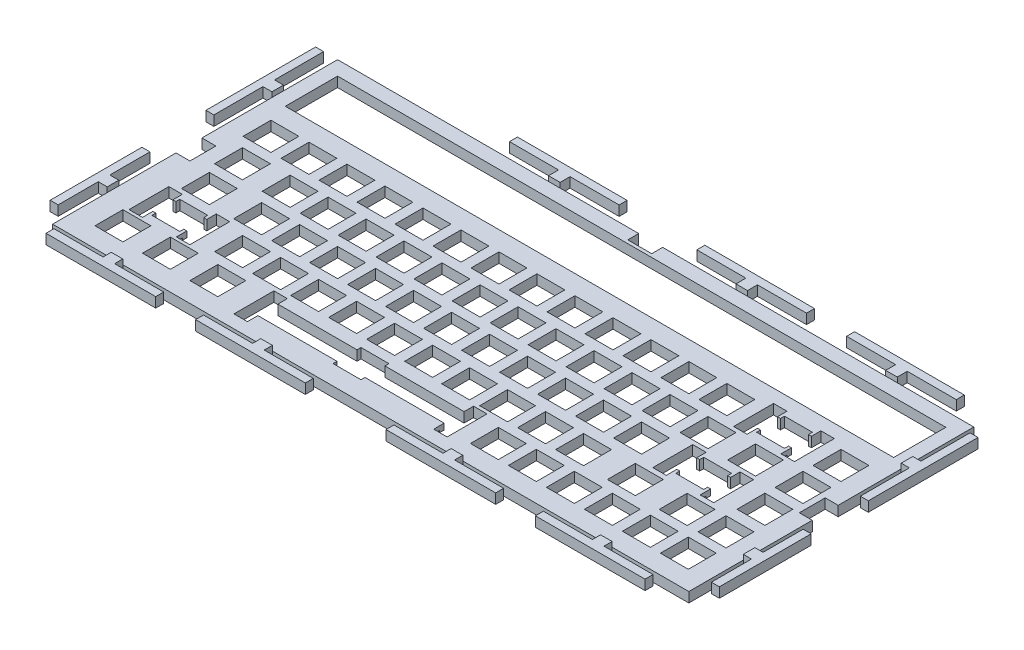
SolidWorks part; units mm, degrees
ref_plane "Front Plane" through (0, 0, 0) normal (0, 0, 1) x (1, 0, 0)
ref_plane "Top Plane" through (0, 0, 0) normal (0, 1, 0) x (1, 0, 0)
ref_plane "Right Plane" through (0, 0, 0) normal (1, 0, 0) x (0, 0, -1)
sketch "Sketch1" plane through (0, 0, 0) normal (0, 1, 0) x (1, 0, 0)
  line L2 (-75.7545, 37.9956) -> (-61.7545, 37.9956)
  line L3 (-94.8265, 37.9956) -> (-80.8265, 37.9956)
  line L4 (-94.8265, 37.9956) -> (-94.8265, 51.9956)
  line L5 (-94.8265, 51.9956) -> (-80.8265, 51.9956)
  line L6 (-80.8265, 37.9956) -> (-80.8265, 51.9956)
  line L7 (-75.7545, 37.9956) -> (-75.7545, 51.9956)
  line L8 (-75.7545, 51.9956) -> (-61.7545, 51.9956)
  line L9 (-61.7545, 37.9956) -> (-61.7545, 51.9956)
  line L10 (133.7495, 37.9956) -> (147.7495, 37.9956)
  line L11 (-37.6545, 37.9956) -> (-23.6545, 37.9956)
  line L12 (-56.7045, 37.9956) -> (-42.7045, 37.9956)
  line L13 (-56.7045, 37.9956) -> (-56.7045, 51.9956)
  line L14 (-56.7045, 51.9956) -> (-42.7045, 51.9956)
  line L15 (-42.7045, 37.9956) -> (-42.7045, 51.9956)
  line L16 (-37.6545, 37.9956) -> (-37.6545, 51.9956)
  line L17 (-37.6545, 51.9956) -> (-23.6545, 51.9956)
  line L18 (-23.6545, 37.9956) -> (-23.6545, 51.9956)
  line L19 (133.7495, 37.9956) -> (133.7495, 51.9956)
  line L20 (133.7495, 51.9956) -> (147.7495, 51.9956)
  line L21 (0.4455, 37.9956) -> (14.4455, 37.9956)
  line L22 (-18.6045, 37.9956) -> (-4.6045, 37.9956)
  line L23 (-18.6045, 37.9956) -> (-18.6045, 51.9956)
  line L24 (-18.6045, 51.9956) -> (-4.6045, 51.9956)
  line L25 (-4.6045, 37.9956) -> (-4.6045, 51.9956)
  line L26 (0.4455, 37.9956) -> (0.4455, 51.9956)
  line L27 (0.4455, 51.9956) -> (14.4455, 51.9956)
  line L28 (14.4455, 37.9956) -> (14.4455, 51.9956)
  line L29 (147.7495, 37.9956) -> (147.7495, 51.9956)
  line L30 (38.5455, 37.9956) -> (52.5455, 37.9956)
  line L31 (19.4955, 37.9956) -> (33.4955, 37.9956)
  line L32 (19.4955, 37.9956) -> (19.4955, 51.9956)
  line L33 (19.4955, 51.9956) -> (33.4955, 51.9956)
  line L34 (33.4955, 37.9956) -> (33.4955, 51.9956)
  line L35 (38.5455, 37.9956) -> (38.5455, 51.9956)
  line L36 (38.5455, 51.9956) -> (52.5455, 51.9956)
  line L37 (52.5455, 37.9956) -> (52.5455, 51.9956)
  line L38 (147.7495, 44.9956) -> (154.1495, 44.9956) construction
  line L39 (167.1835, 18.9456) -> (181.1835, 18.9456)
  line L40 (167.1835, 18.9456) -> (167.1835, 32.9456)
  line L41 (76.6455, 37.9956) -> (90.6455, 37.9956)
  line L42 (57.5955, 37.9956) -> (71.5955, 37.9956)
  line L43 (57.5955, 37.9956) -> (57.5955, 51.9956)
  line L44 (57.5955, 51.9956) -> (71.5955, 51.9956)
  line L45 (71.5955, 37.9956) -> (71.5955, 51.9956)
  line L46 (76.6455, 37.9956) -> (76.6455, 51.9956)
  line L47 (76.6455, 51.9956) -> (90.6455, 51.9956)
  line L48 (90.6455, 37.9956) -> (90.6455, 51.9956)
  line L49 (167.1835, 32.9456) -> (181.1835, 32.9456)
  line L50 (114.7225, 37.9956) -> (128.7225, 37.9956)
  line L51 (95.6955, 37.9956) -> (109.6955, 37.9956)
  line L52 (95.6955, 37.9956) -> (95.6955, 51.9956)
  line L53 (95.6955, 51.9956) -> (109.6955, 51.9956)
  line L54 (109.6955, 37.9956) -> (109.6955, 51.9956)
  line L55 (114.7225, 37.9956) -> (114.7225, 51.9956)
  line L56 (114.7225, 51.9956) -> (128.7225, 51.9956)
  line L57 (128.7225, 37.9956) -> (128.7225, 51.9956)
  line L58 (181.1835, 18.9456) -> (181.1835, 32.9456)
  line L59 (157.3735, 25.9456) -> (167.1835, 25.9456) construction
  line L73 (162.3995, 52.2456) -> (176.3995, 52.2456)
  line L75 (176.3995, 38.2456) -> (162.3995, 38.2456)
  line L77 (176.3995, 52.2456) -> (176.3995, 50.2456)
  line L78 (176.3995, 50.2456) -> (177.8995, 50.2456)
  line L79 (177.8995, 50.2456) -> (177.8995, 54.9956)
  line L80 (177.8995, 54.9956) -> (184.6495, 54.9956)
  line L81 (184.6495, 54.9956) -> (184.6495, 34.9956)
  line L82 (184.6495, 34.9956) -> (177.8995, 34.9956)
  line L83 (177.8995, 34.9956) -> (177.8995, 40.2456)
  line L84 (177.8995, 40.2456) -> (176.3995, 40.2456)
  line L85 (176.3995, 40.2456) -> (176.3995, 38.2456)
  line L86 (162.3995, 52.2456) -> (162.3995, 50.2456)
  line L87 (160.8995, 54.9956) -> (160.8995, 50.2456)
  line L88 (160.8995, 50.2456) -> (162.3995, 50.2456)
  line L89 (160.8995, 54.9956) -> (154.1495, 54.9956)
  line L90 (154.1495, 54.9956) -> (154.1495, 34.9956)
  line L91 (154.1495, 34.9956) -> (160.8995, 34.9956)
  line L92 (160.8995, 34.9956) -> (160.8995, 40.2456)
  line L93 (160.8995, 40.2456) -> (162.3995, 40.2456)
  line L94 (162.3995, 40.2456) -> (162.3995, 38.2456)
  line L116 (-47.1265, 18.9456) -> (-33.1265, 18.9456)
  line L117 (-66.1765, 18.9456) -> (-52.1765, 18.9456)
  line L118 (-66.1765, 18.9456) -> (-66.1765, 32.9456)
  line L119 (-66.1765, 32.9456) -> (-52.1765, 32.9456)
  line L120 (-52.1765, 18.9456) -> (-52.1765, 32.9456)
  line L121 (-47.1265, 18.9456) -> (-47.1265, 32.9456)
  line L122 (-47.1265, 32.9456) -> (-33.1265, 32.9456)
  line L123 (-33.1265, 18.9456) -> (-33.1265, 32.9456)
  line L125 (-9.0515, 18.9456) -> (4.9485, 18.9456)
  line L126 (-28.0765, 18.9456) -> (-14.0765, 18.9456)
  line L127 (-28.0765, 18.9456) -> (-28.0765, 32.9456)
  line L128 (-28.0765, 32.9456) -> (-14.0765, 32.9456)
  line L129 (-14.0765, 18.9456) -> (-14.0765, 32.9456)
  line L130 (-9.0515, 18.9456) -> (-9.0515, 32.9456)
  line L131 (-9.0515, 32.9456) -> (4.9485, 32.9456)
  line L132 (4.9485, 18.9456) -> (4.9485, 32.9456)
  line L135 (29.0735, 18.9456) -> (43.0735, 18.9456)
  line L136 (9.9485, 18.9456) -> (23.9485, 18.9456)
  line L137 (9.9485, 18.9456) -> (9.9485, 32.9456)
  line L138 (9.9485, 32.9456) -> (23.9485, 32.9456)
  line L139 (23.9485, 18.9456) -> (23.9485, 32.9456)
  line L140 (29.0735, 18.9456) -> (29.0735, 32.9456)
  line L141 (29.0735, 32.9456) -> (43.0735, 32.9456)
  line L142 (43.0735, 18.9456) -> (43.0735, 32.9456)
  line L144 (67.1485, 18.9456) -> (81.1485, 18.9456)
  line L145 (48.1235, 18.9456) -> (62.1235, 18.9456)
  line L146 (48.1235, 18.9456) -> (48.1235, 32.9456)
  line L147 (48.1235, 32.9456) -> (62.1235, 32.9456)
  line L148 (62.1235, 18.9456) -> (62.1235, 32.9456)
  line L149 (67.1485, 18.9456) -> (67.1485, 32.9456)
  line L150 (67.1485, 32.9456) -> (81.1485, 32.9456)
  line L151 (81.1485, 18.9456) -> (81.1485, 32.9456)
  line L152 (159.9865, 14.1456) -> (173.9865, 14.1456)
  line L153 (-42.3635, -0.1044) -> (-28.3635, -0.1044)
  line L154 (-61.4135, -0.1044) -> (-47.4135, -0.1044)
  line L155 (105.2735, 18.9456) -> (119.2735, 18.9456)
  line L156 (86.2235, 18.9456) -> (100.2235, 18.9456)
  line L157 (86.2235, 18.9456) -> (86.2235, 32.9456)
  line L158 (86.2235, 32.9456) -> (100.2235, 32.9456)
  line L159 (100.2235, 18.9456) -> (100.2235, 32.9456)
  line L160 (105.2735, 18.9456) -> (105.2735, 32.9456)
  line L161 (105.2735, 32.9456) -> (119.2735, 32.9456)
  line L162 (119.2735, 18.9456) -> (119.2735, 32.9456)
  line L163 (-61.4135, -0.1044) -> (-61.4135, 13.8956)
  line L172 (-94.8265, 37.9956) -> (-94.8265, 32.9456) construction
  line L173 (-61.4135, 13.8956) -> (-47.4135, 13.8956)
  line L174 (-47.4135, -0.1044) -> (-47.4135, 13.8956)
  line L175 (-90.0635, 18.9456) -> (-76.0635, 18.9456)
  line L176 (-90.0635, 18.9456) -> (-90.0635, 32.9456)
  line L177 (-90.0635, 32.9456) -> (-76.0635, 32.9456)
  line L178 (-76.0635, 18.9456) -> (-76.0635, 32.9456)
  line L179 (-94.8265, 32.9456) -> (-90.0635, 32.9456) construction
  line L180 (124.3235, 18.9456) -> (138.3235, 18.9456)
  line L185 (124.3235, 18.9456) -> (124.3235, 32.9456)
  line L186 (124.3235, 32.9456) -> (138.3235, 32.9456)
  line L187 (138.3235, 18.9456) -> (138.3235, 32.9456)
  line L188 (-42.3635, -0.1044) -> (-42.3635, 13.8956)
  line L189 (143.3735, 18.9456) -> (157.3735, 18.9456)
  line L190 (143.3735, 18.9456) -> (143.3735, 32.9456)
  line L191 (143.3735, 32.9456) -> (157.3735, 32.9456)
  line L192 (157.3735, 18.9456) -> (157.3735, 32.9456)
  line L193 (-42.3635, 13.8956) -> (-28.3635, 13.8956)
  line L194 (-28.3635, -0.1044) -> (-28.3635, 13.8956)
  line L195 (-4.2635, -0.1044) -> (9.7365, -0.1044)
  line L196 (-23.3135, -0.1044) -> (-9.3135, -0.1044)
  line L197 (-23.3135, -0.1044) -> (-23.3135, 13.8956)
  line L198 (-23.3135, 13.8956) -> (-9.3135, 13.8956)
  line L199 (-9.3135, -0.1044) -> (-9.3135, 13.8956)
  line L200 (-4.2635, -0.1044) -> (-4.2635, 13.8956)
  line L201 (-4.2635, 13.8956) -> (9.7365, 13.8956)
  line L202 (9.7365, -0.1044) -> (9.7365, 13.8956)
  line L203 (33.8365, -0.1044) -> (47.8365, -0.1044)
  line L204 (14.7865, -0.1044) -> (28.7865, -0.1044)
  line L205 (14.7865, -0.1044) -> (14.7865, 13.8956)
  line L206 (14.7865, 13.8956) -> (28.7865, 13.8956)
  line L207 (28.7865, -0.1044) -> (28.7865, 13.8956)
  line L208 (33.8365, -0.1044) -> (33.8365, 13.8956)
  line L209 (33.8365, 13.8956) -> (47.8365, 13.8956)
  line L210 (47.8365, -0.1044) -> (47.8365, 13.8956)
  line L211 (71.9365, -0.1044) -> (85.9365, -0.1044)
  line L212 (52.8865, -0.1044) -> (66.8865, -0.1044)
  line L213 (52.8865, -0.1044) -> (52.8865, 13.8956)
  line L214 (52.8865, 13.8956) -> (66.8865, 13.8956)
  line L215 (66.8865, -0.1044) -> (66.8865, 13.8956)
  line L216 (71.9365, -0.1044) -> (71.9365, 13.8956)
  line L217 (71.9365, 13.8956) -> (85.9365, 13.8956)
  line L218 (85.9365, -0.1044) -> (85.9365, 13.8956)
  line L219 (110.0365, -0.1044) -> (124.0365, -0.1044)
  line L220 (90.9865, -0.1044) -> (104.9865, -0.1044)
  line L221 (90.9865, -0.1044) -> (90.9865, 13.8956)
  line L222 (90.9865, 13.8956) -> (104.9865, 13.8956)
  line L223 (104.9865, -0.1044) -> (104.9865, 13.8956)
  line L224 (110.0365, -0.1044) -> (110.0365, 13.8956)
  line L225 (110.0365, 13.8956) -> (124.0365, 13.8956)
  line L226 (124.0365, -0.1044) -> (124.0365, 13.8956)
  line L227 (-87.6075, -0.1044) -> (-73.6075, -0.1044)
  line L228 (-87.6075, -0.1044) -> (-87.6075, 13.8956)
  line L229 (-87.6075, 13.8956) -> (-73.6075, 13.8956)
  line L230 (-73.6075, -0.1044) -> (-73.6075, 13.8956)
  line L231 (-90.0635, 18.9456) -> (-90.0635, 13.8956) construction
  line L232 (129.0865, -0.1044) -> (143.0865, -0.1044)
  line L233 (129.0865, -0.1044) -> (129.0865, 13.8956)
  line L234 (129.0865, 13.8956) -> (143.0865, 13.8956)
  line L235 (143.0865, -0.1044) -> (143.0865, 13.8956)
  line L240 (-90.0635, 13.8956) -> (-87.6075, 13.8956) construction
  line L241 (173.9865, 0.1456) -> (159.9865, 0.1456)
  line L242 (173.9865, 14.1456) -> (173.9865, 12.1456)
  line L243 (173.9865, 12.1456) -> (175.4865, 12.1456)
  line L244 (175.4865, 12.1456) -> (175.4865, 16.8956)
  line L245 (175.4865, 16.8956) -> (182.2365, 16.8956)
  line L246 (182.2365, 16.8956) -> (182.2365, -3.1044)
  line L247 (182.2365, -3.1044) -> (175.4865, -3.1044)
  line L248 (175.4865, -3.1044) -> (175.4865, 2.1456)
  line L249 (175.4865, 2.1456) -> (173.9865, 2.1456)
  line L250 (173.9865, 2.1456) -> (173.9865, 0.1456)
  line L251 (159.9865, 14.1456) -> (159.9865, 12.1456)
  line L252 (158.4865, 16.8956) -> (158.4865, 12.1456)
  line L253 (158.4865, 12.1456) -> (159.9865, 12.1456)
  line L254 (158.4865, 16.8956) -> (151.7365, 16.8956)
  line L255 (151.7365, 16.8956) -> (151.7365, -3.1044)
  line L256 (151.7365, -3.1044) -> (158.4865, -3.1044)
  line L257 (158.4865, -3.1044) -> (158.4865, 2.1456)
  line L258 (158.4865, 2.1456) -> (159.9865, 2.1456)
  line L259 (159.9865, 2.1456) -> (159.9865, 0.1456)
  line L260 (143.0865, 12.1456) -> (151.7365, 12.1456) construction
  line L262 (-32.8385, -19.1544) -> (-18.8385, -19.1544)
  line L263 (-51.8885, -19.1544) -> (-37.8885, -19.1544)
  line L264 (-51.8885, -19.1544) -> (-51.8885, -5.1544)
  line L265 (-51.8885, -5.1544) -> (-37.8885, -5.1544)
  line L266 (-37.8885, -19.1544) -> (-37.8885, -5.1544)
  line L267 (-32.8385, -19.1544) -> (-32.8385, -5.1544)
  line L268 (-32.8385, -5.1544) -> (-18.8385, -5.1544)
  line L269 (-18.8385, -19.1544) -> (-18.8385, -5.1544)
  line L270 (5.2615, -19.1544) -> (19.2615, -19.1544)
  line L271 (-13.7885, -19.1544) -> (0.2115, -19.1544)
  line L272 (-13.7885, -19.1544) -> (-13.7885, -5.1544)
  line L273 (-13.7885, -5.1544) -> (0.2115, -5.1544)
  line L274 (0.2115, -19.1544) -> (0.2115, -5.1544)
  line L275 (5.2615, -19.1544) -> (5.2615, -5.1544)
  line L276 (5.2615, -5.1544) -> (19.2615, -5.1544)
  line L277 (19.2615, -19.1544) -> (19.2615, -5.1544)
  line L278 (43.3615, -19.1544) -> (57.3615, -19.1544)
  line L279 (24.3115, -19.1544) -> (38.3115, -19.1544)
  line L280 (24.3115, -19.1544) -> (24.3115, -5.1544)
  line L281 (24.3115, -5.1544) -> (38.3115, -5.1544)
  line L282 (38.3115, -19.1544) -> (38.3115, -5.1544)
  line L283 (43.3615, -19.1544) -> (43.3615, -5.1544)
  line L284 (43.3615, -5.1544) -> (57.3615, -5.1544)
  line L285 (57.3615, -19.1544) -> (57.3615, -5.1544)
  line L286 (81.4615, -19.6544) -> (95.4615, -19.6544)
  line L287 (62.4115, -19.6544) -> (76.4115, -19.6544)
  line L288 (62.4115, -19.6544) -> (62.4115, -5.6544)
  line L289 (62.4115, -5.6544) -> (76.4115, -5.6544)
  line L290 (76.4115, -19.6544) -> (76.4115, -5.6544)
  line L291 (81.4615, -19.6544) -> (81.4615, -5.6544)
  line L292 (81.4615, -5.6544) -> (95.4615, -5.6544)
  line L293 (95.4615, -19.6544) -> (95.4615, -5.6544)
  line L294 (119.5615, -19.6544) -> (133.5615, -19.6544)
  line L295 (100.5115, -19.6544) -> (114.5115, -19.6544)
  line L296 (100.5115, -19.6544) -> (100.5115, -5.6544)
  line L297 (100.5115, -5.6544) -> (114.5115, -5.6544)
  line L298 (114.5115, -19.6544) -> (114.5115, -5.6544)
  line L299 (119.5615, -19.6544) -> (119.5615, -5.6544)
  line L300 (119.5615, -5.6544) -> (133.5615, -5.6544)
  line L301 (133.5615, -19.6544) -> (133.5615, -5.6544)
  line L306 (-83.3445, -5.1544) -> (-69.3445, -5.1544)
  line L307 (145.5235, -19.6544) -> (159.5235, -19.6544)
  line L308 (145.5235, -19.6544) -> (145.5235, -5.6544)
  line L309 (145.5235, -5.6544) -> (159.5235, -5.6544)
  line L310 (159.5235, -19.6544) -> (159.5235, -5.6544)
  line L311 (-69.3445, -19.1544) -> (-83.3445, -19.1544)
  line L331 (171.4855, -19.6544) -> (185.4855, -19.6544)
  line L332 (171.4855, -19.6544) -> (171.4855, -5.6544)
  line L333 (171.4855, -5.6544) -> (185.4855, -5.6544)
  line L334 (185.4855, -19.6544) -> (185.4855, -5.6544)
  line L335 (159.5235, -12.6544) -> (171.4855, -12.6544) construction
  line L336 (-61.4135, -0.1044) -> (-61.4135, -5.1544) construction
  line L337 (-61.4135, -5.1544) -> (-51.8885, -5.1544) construction
  line L338 (-104.4215, 94.9896) -> (-117.5239, 94.9896) construction
  line L339 (-97.2765, 61.6456) -> (207.7235, 61.6456)
  line L340 (190.9955, 18.9456) -> (204.9955, 18.9456)
  line L341 (190.9955, 18.9456) -> (190.9955, 32.9456)
  line L342 (190.9955, 32.9456) -> (204.9955, 32.9456)
  line L343 (204.9955, 18.9456) -> (204.9955, 32.9456)
  line L344 (181.1835, 25.9456) -> (190.9955, 25.9456) construction
  line L345 (190.9745, 37.9956) -> (204.9745, 37.9956)
  line L346 (190.9745, 37.9956) -> (190.9745, 51.9956)
  line L347 (190.9745, 51.9956) -> (204.9745, 51.9956)
  line L348 (204.9745, 37.9956) -> (204.9745, 51.9956)
  line L349 (184.6495, 44.9956) -> (190.9745, 44.9956) construction
  line L350 (190.9425, -0.1044) -> (204.9425, -0.1044)
  line L351 (190.9425, -0.1044) -> (190.9425, 13.8956)
  line L352 (190.9425, 13.8956) -> (204.9425, 13.8956)
  line L353 (204.9425, -0.1044) -> (204.9425, 13.8956)
  line L354 (182.2365, 6.8956) -> (190.9425, 6.8956) construction
  line L355 (190.9855, -19.6544) -> (204.9855, -19.6544)
  line L356 (190.9855, -19.6544) -> (190.9855, -5.6544)
  line L357 (190.9855, -5.6544) -> (204.9855, -5.6544)
  line L358 (204.9855, -19.6544) -> (204.9855, -5.6544)
  line L359 (185.4855, -12.6544) -> (190.9855, -12.6544) construction
  line L360 (-69.3445, -5.1544) -> (-69.3445, -7.1544)
  line L361 (-69.3445, -7.1544) -> (-67.8445, -7.1544)
  line L362 (-67.8445, -7.1544) -> (-67.8445, -2.4044)
  line L363 (-67.8445, -2.4044) -> (-61.0945, -2.4044)
  line L364 (-61.0945, -2.4044) -> (-61.0945, -22.4044)
  line L365 (-61.0945, -22.4044) -> (-67.8445, -22.4044)
  line L366 (-67.8445, -22.4044) -> (-67.8445, -17.1544)
  line L367 (-67.8445, -17.1544) -> (-69.3445, -17.1544)
  line L368 (-69.3445, -17.1544) -> (-69.3445, -19.1544)
  line L369 (-83.3445, -5.1544) -> (-83.3445, -7.1544)
  line L370 (-84.8445, -2.4044) -> (-84.8445, -7.1544)
  line L371 (-84.8445, -7.1544) -> (-83.3445, -7.1544)
  line L372 (-84.8445, -2.4044) -> (-91.5945, -2.4044)
  line L373 (-91.5945, -2.4044) -> (-91.5945, -22.4044)
  line L374 (-91.5945, -22.4044) -> (-84.8445, -22.4044)
  line L375 (-84.8445, -22.4044) -> (-84.8445, -17.1544)
  line L376 (-84.8445, -17.1544) -> (-83.3445, -17.1544)
  line L377 (-83.3445, -17.1544) -> (-83.3445, -19.1544)
  line L378 (-93.0945, -37.9544) -> (-79.0945, -37.9544)
  line L379 (-93.0945, -37.9544) -> (-93.0945, -23.9544)
  line L380 (-93.0945, -23.9544) -> (-79.0945, -23.9544)
  line L381 (-79.0945, -37.9544) -> (-79.0945, -23.9544)
  line L382 (-69.2945, -37.9544) -> (-55.2945, -37.9544)
  line L383 (-69.2945, -37.9544) -> (-69.2945, -23.9544)
  line L384 (-69.2945, -23.9544) -> (-55.2945, -23.9544)
  line L385 (-55.2945, -37.9544) -> (-55.2945, -23.9544)
  line L390 (-45.4945, -37.9544) -> (-31.4945, -37.9544)
  line L391 (-45.4945, -37.9544) -> (-45.4945, -23.9544)
  line L392 (-45.4945, -23.9544) -> (-31.4945, -23.9544)
  line L393 (-31.4945, -37.9544) -> (-31.4945, -23.9544)
  line L394 (-55.2945, -23.9544) -> (-45.4945, -23.9544) construction
  line L395 (26.4395, -24.1144) -> (40.4395, -24.1144)
  line L396 (40.4395, -38.1144) -> (26.4395, -38.1144)
  line L397 (40.4395, -24.1144) -> (40.4395, -26.1144)
  line L398 (40.4395, -26.1144) -> (80.1235, -26.1144)
  line L399 (80.1235, -26.1144) -> (80.1235, -21.3644)
  line L400 (80.1235, -21.3644) -> (86.8735, -21.3644)
  line L401 (86.8735, -21.3644) -> (86.8735, -41.3644)
  line L402 (86.8735, -41.3644) -> (80.1235, -41.3644)
  line L403 (80.1235, -41.3644) -> (80.1235, -36.1144)
  line L404 (80.1235, -36.1144) -> (40.4395, -36.1144)
  line L405 (40.4395, -36.1144) -> (40.4395, -38.1144)
  line L406 (26.4395, -24.1144) -> (26.4395, -26.1144)
  line L407 (-13.2445, -21.3644) -> (-13.2445, -26.1144)
  line L408 (-13.2445, -26.1144) -> (26.4395, -26.1144)
  line L409 (-13.2445, -21.3644) -> (-19.9945, -21.3644)
  line L410 (-19.9945, -21.3644) -> (-19.9945, -41.3644)
  line L411 (-19.9945, -41.3644) -> (-13.2445, -41.3644)
  line L412 (-13.2445, -41.3644) -> (-13.2445, -36.1144)
  line L413 (-13.2445, -36.1144) -> (26.4395, -36.1144)
  line L414 (26.4395, -36.1144) -> (26.4395, -38.1144)
  line L415 (95.5435, -38.3644) -> (109.5435, -38.3644)
  line L416 (95.5435, -38.3644) -> (95.5435, -24.3644)
  line L417 (95.5435, -24.3644) -> (109.5435, -24.3644)
  line L418 (109.5435, -38.3644) -> (109.5435, -24.3644)
  line L419 (86.8735, -31.3644) -> (95.5435, -31.3644) construction
  line L420 (114.5935, -38.3644) -> (128.5935, -38.3644)
  line L421 (114.5935, -38.3644) -> (114.5935, -24.3644)
  line L422 (114.5935, -24.3644) -> (128.5935, -24.3644)
  line L423 (128.5935, -38.3644) -> (128.5935, -24.3644)
  line L424 (114.5935, -31.3644) -> (109.5435, -31.3644) construction
  line L425 (133.6435, -38.3644) -> (147.6435, -38.3644)
  line L426 (133.6435, -38.3644) -> (133.6435, -24.3644)
  line L427 (133.6435, -24.3644) -> (147.6435, -24.3644)
  line L428 (147.6435, -38.3644) -> (147.6435, -24.3644)
  line L429 (152.6935, -38.3644) -> (166.6935, -38.3644)
  line L430 (152.6935, -38.3644) -> (152.6935, -24.3644)
  line L431 (152.6935, -24.3644) -> (166.6935, -24.3644)
  line L432 (166.6935, -38.3644) -> (166.6935, -24.3644)
  line L433 (171.7435, -38.3644) -> (185.7435, -38.3644)
  line L434 (171.7435, -38.3644) -> (171.7435, -24.3644)
  line L435 (171.7435, -24.3644) -> (185.7435, -24.3644)
  line L436 (185.7435, -38.3644) -> (185.7435, -24.3644)
  line L437 (190.7935, -38.3644) -> (204.7935, -38.3644)
  line L438 (190.7935, -38.3644) -> (190.7935, -24.3644)
  line L439 (190.7935, -24.3644) -> (204.7935, -24.3644)
  line L440 (204.7935, -38.3644) -> (204.7935, -24.3644)
  line L441 (-97.2765, 61.6456) -> (-97.2765, 87.8456)
  line L442 (-97.2765, 87.8456) -> (207.7235, 87.8456)
  line L443 (207.7235, 61.6456) -> (207.7235, 87.8456)
  line L444 (-104.4215, 94.9896) -> (214.5785, 94.9896)
  line L445 (-104.4215, 94.9896) -> (-104.4215, -47.8854)
  line L446 (-104.4215, -47.8854) -> (214.5785, -47.8854)
  line L447 (214.5785, 94.9896) -> (214.5785, -47.8854)
  line L448 (-117.5239, 94.9896) -> (-117.5239, 25.8096) construction
  line L449 (-104.4215, -47.8854) -> (-117.5239, -47.8854) construction
  line L450 (-117.5239, -47.8854) -> (-117.5239, 14.6046) construction
  line L451 (-150.5498, 25.8096) -> (-98.6233, 25.8096) construction
  line L452 (-150.5498, 14.6046) -> (-97.2765, 14.6046) construction
  line L453 (-104.4215, 94.9896) -> (-104.4215, 60.3996) construction
  point P115 (128.7225, 44.9956)
  point P116 (154.1495, 44.9956)
  dimension "D1" = 14
  dimension "D2" = 20
  dimension "D3" = 4.75
  dimension "D4" = 6.75
  dimension "D5" = 1.5
  dimension "D6" = 2
  dimension "D13" = 14
  dimension "D14" = 14
  dimension "D15" = 5.072
  dimension "D16" = 14
  dimension "D17" = 5.05
  dimension "D18" = 5.05
  dimension "D19" = 14
  dimension "D20" = 4.763
  dimension "D21" = 5.05
  dimension "D22" = 9.887
  dimension "D23" = 26.2
  dimension "D24" = 14
  dimension "D25" = 14
  dimension "D26" = 5.05
  dimension "D27" = 5.05
  dimension "D28" = 5.05
  dimension "D29" = 5.05
  dimension "D30" = 5.05
  dimension "D31" = 5.05
  dimension "D32" = 5.05
  dimension "D33" = 5.05
  dimension "D34" = 5.05
  dimension "D35" = 5.027
  dimension "D36" = 5.05
  dimension "D37" = 5.05
  dimension "D38" = 5.025
  dimension "D39" = 5
  dimension "D40" = 5.125
  dimension "D41" = 5.05
  dimension "D42" = 5.025
  dimension "D43" = 5.075
  dimension "D44" = 5.05
  dimension "D45" = 5.05
  dimension "D46" = 5.027
  dimension "D47" = 14.65
  dimension "D48" = 14
  dimension "D49" = 9.81
  dimension "D50" = 12.194
  dimension "D51" = 5.05
  dimension "D52" = 5.05
  dimension "D53" = 5.05
  dimension "D54" = 5.05
  dimension "D55" = 5.05
  dimension "D56" = 5.05
  dimension "D57" = 5.05
  dimension "D58" = 5.05
  dimension "D59" = 5.05
  dimension "D60" = 5.05
  dimension "D61" = 14
  dimension "D62" = 20
  dimension "D63" = 5.05
  dimension "D64" = 2.456
  dimension "D65" = 4.75
  dimension "D66" = 6.75
  dimension "D67" = 1.5
  dimension "D68" = 2
  dimension "D69" = 16.9
  dimension "D70" = 14
  dimension "D71" = 5.05
  dimension "D72" = 5.05
  dimension "D73" = 5.05
  dimension "D74" = 5.05
  dimension "D75" = 5.05
  dimension "D76" = 5.05
  dimension "D77" = 5.05
  dimension "D78" = 5.05
  dimension "D79" = 5.05
  dimension "D80" = 11.962
  dimension "D81" = 20
  dimension "D82" = 14
  dimension "D83" = 11.962
  dimension "D84" = 14
  dimension "D85" = 14
  dimension "D86" = 9.812
  dimension "D87" = 14
  dimension "D88" = 14.575
  dimension "D89" = 4.75
  dimension "D90" = 14
  dimension "D91" = 6.75
  dimension "D92" = 14
  dimension "D93" = 16.956
  dimension "D94" = 14
  dimension "D95" = 5.5
  dimension "D96" = 5.05
  dimension "D97" = 5.05
  dimension "D98" = 9.525
  dimension "D99" = 1.5
  dimension "D100" = 2
  dimension "D101" = 5.05
  dimension "D102" = 9.206
  dimension "D103" = 5.05
  dimension "D104" = 14
  dimension "D105" = 14
  dimension "D106" = 14
  dimension "D107" = 14
  dimension "D108" = 1.5
  dimension "D109" = 9.8
  dimension "D110" = 5.05
  dimension "D111" = 9.8
  dimension "D112" = 5.05
  dimension "D113" = 5.05
  dimension "D114" = 14
  dimension "D115" = 14
  dimension "D116" = 20
  dimension "D117" = 4.75
  dimension "D118" = 6.75
  dimension "D119" = 39.684
  dimension "D120" = 2
  dimension "D121" = 5.05
  dimension "D122" = 11.5
  dimension "D123" = 14
  dimension "D124" = 8.67
  dimension "D125" = 5.25
  dimension "D126" = 14
  dimension "D127" = 5.05
  dimension "D128" = 14
  dimension "D129" = 14
  dimension "D130" = 14
  dimension "D131" = 14
  dimension "D132" = 5.05
  dimension "D133" = 5.05
  dimension "D134" = 5.05
  dimension "D135" = 5.05
  dimension "D136" = 4.8
  dimension "D137" = 5.25
  dimension "D138" = 5.25
  dimension "D139" = 5.25
  dimension "D140" = 305
  dimension "D141" = 9.65
  dimension "D142" = 142.875
  dimension "D143" = 319
  dimension "D144" = 7.144
  dimension "D145" = 7.145
  dimension "D146" = 2.45
  dimension "D147" = 69.18
  dimension "D148" = 62.49
extrude "Boss-Extrude2" add sketch "Sketch1" along normal mid plane 5
sketch "Sketch2" plane through (0, 2.5, 0) normal (0, 1, 0) x (1, 0, 0)
  line L0 (-104.4215, 25.7896) -> (-104.4215, 14.6146) construction
  line L1 (-104.4215, -47.8854) -> (-104.4215, -20.4854) construction
  line L2 (-104.4215, 94.9896) -> (-104.4215, -47.8854) construction
  line L14 (-107.4215, 20.2021) -> (-104.4215, 20.2021) construction
  line L16 (-107.4215, 31.2421) -> (-107.4215, 9.1621) construction
  line L25 (214.5785, 64.3896) -> (214.5785, 58.5896)
  line L26 (55.1185, 125.3194) -> (55.1185, -78.0627) construction
  line L44 (214.5785, 58.5896) -> (218.6785, 58.5896)
  line L45 (218.6785, 58.5896) -> (218.6785, 33.9896)
  line L46 (218.6785, 33.9896) -> (222.6785, 33.9896)
  line L47 (222.6785, 33.9896) -> (222.6785, 88.9896)
  line L48 (55.0785, 94.9896) -> (55.0785, -47.8854) construction
  line L49 (214.5785, 94.9896) -> (-104.4215, 94.9896) construction
  line L50 (-104.4215, -47.8854) -> (214.5785, -47.8854) construction
  line L51 (55.1185, 23.6283) -> (270.1989, 23.6283) construction
  line L52 (55.1185, 23.6283) -> (-168.679, 23.6283) construction
  line L55 (45.7235, 94.9896) -> (56.8285, 94.9896) construction
  line L56 (51.276, 94.9896) -> (51.276, 98.9896) construction
  line L57 (40.236, 98.9896) -> (62.316, 98.9896) construction
  line L74 (222.6785, 88.9896) -> (218.6785, 88.9896)
  line L75 (214.5785, 94.9896) -> (176.1966, 94.9896) construction
  line L124 (55.0785, -47.8854) -> (95.4285, -47.8854) construction
  line L125 (-104.4215, 67.8896) -> (-104.4215, 62.0896)
  line L127 (45.7225, -47.8854) -> (56.8335, -47.8854) construction
  line L128 (51.278, -47.8854) -> (51.278, -52.8854) construction
  line L129 (40.276, -52.8854) -> (62.356, -52.8854) construction
  line L134 (-104.4215, 62.0896) -> (-108.9215, 62.0896)
  line L135 (-108.9215, 62.0896) -> (-108.9215, 37.4896)
  line L136 (-108.9215, 37.4896) -> (-112.9215, 37.4896)
  line L137 (-112.9215, 37.4896) -> (-112.9215, 92.4896)
  line L138 (-112.9215, 92.4896) -> (-108.9215, 92.4896)
  line L139 (-108.9215, 92.4896) -> (-108.9215, 67.8896)
  line L140 (-108.9215, 67.8896) -> (-104.4215, 67.8896)
  line L141 (-104.4215, 94.9896) -> (-104.4215, 67.8896) construction
  line L142 (-104.4215, -14.6854) -> (-104.4215, -20.4854)
  line L143 (-104.4215, -20.4854) -> (-108.9215, -20.4854)
  line L144 (-108.9215, -20.4854) -> (-108.9215, -40.5854)
  line L145 (-108.9215, -40.5854) -> (-112.9215, -40.5854)
  line L146 (-112.9215, -40.5854) -> (-112.9215, 5.4146)
  line L147 (-112.9215, 5.4146) -> (-108.9215, 5.4146)
  line L148 (-108.9215, 5.4146) -> (-108.9215, -14.6854)
  line L149 (-108.9215, -14.6854) -> (-104.4215, -14.6854)
  line L150 (1.3585, 94.9896) -> (7.1585, 94.9896)
  line L151 (7.1585, 94.9896) -> (7.1585, 99.9896)
  line L152 (7.1585, 99.9896) -> (31.7585, 99.9896)
  line L153 (31.7585, 99.9896) -> (31.7585, 103.9896)
  line L154 (31.7585, 103.9896) -> (-23.2415, 103.9896)
  line L155 (-23.2415, 103.9896) -> (-23.2415, 99.9896)
  line L156 (-23.2415, 99.9896) -> (1.3585, 99.9896)
  line L157 (1.3585, 99.9896) -> (1.3585, 94.9896)
  line L158 (55.0785, 94.9896) -> (7.1585, 94.9896) construction
  line L166 (-75.0215, -47.8854) -> (-69.2215, -47.8854)
  line L167 (-69.2215, -47.8854) -> (-69.2215, -51.9854)
  line L168 (-69.2215, -51.9854) -> (-44.6215, -51.9854)
  line L169 (-44.6215, -51.9854) -> (-44.6215, -55.9854)
  line L170 (-44.6215, -55.9854) -> (-99.6215, -55.9854)
  line L171 (-99.6215, -55.9854) -> (-99.6215, -51.9854)
  line L172 (-99.6215, -51.9854) -> (-75.0215, -51.9854)
  line L173 (-75.0215, -51.9854) -> (-75.0215, -47.8854)
  line L174 (-0.0215, -47.8854) -> (5.7785, -47.8854)
  line L175 (5.7785, -47.8854) -> (5.7785, -51.9854)
  line L176 (5.7785, -51.9854) -> (30.3785, -51.9854)
  line L177 (30.3785, -51.9854) -> (30.3785, -55.9854)
  line L178 (30.3785, -55.9854) -> (-24.6215, -55.9854)
  line L179 (-24.6215, -55.9854) -> (-24.6215, -51.9854)
  line L180 (-24.6215, -51.9854) -> (-0.0215, -51.9854)
  line L181 (-0.0215, -51.9854) -> (-0.0215, -47.8854)
  line L182 (-104.4215, -47.8854) -> (-75.0215, -47.8854) construction
  line L183 (95.4285, -47.8854) -> (101.2285, -47.8854)
  line L184 (101.2285, -47.8854) -> (101.2285, -51.9854)
  line L185 (101.2285, -51.9854) -> (125.8285, -51.9854)
  line L186 (125.8285, -51.9854) -> (125.8285, -55.9854)
  line L187 (125.8285, -55.9854) -> (70.8285, -55.9854)
  line L188 (70.8285, -55.9854) -> (70.8285, -51.9854)
  line L189 (70.8285, -51.9854) -> (95.4285, -51.9854)
  line L190 (95.4285, -51.9854) -> (95.4285, -47.8854)
  line L191 (170.3285, -47.8854) -> (176.1285, -47.8854)
  line L192 (176.1285, -47.8854) -> (176.1285, -51.9854)
  line L193 (176.1285, -51.9854) -> (200.7285, -51.9854)
  line L194 (200.7285, -51.9854) -> (200.7285, -55.9854)
  line L195 (200.7285, -55.9854) -> (145.7285, -55.9854)
  line L196 (145.7285, -55.9854) -> (145.7285, -51.9854)
  line L197 (145.7285, -51.9854) -> (170.3285, -51.9854)
  line L198 (170.3285, -51.9854) -> (170.3285, -47.8854)
  line L199 (55.0785, -47.8854) -> (5.7785, -47.8854) construction
  line L200 (95.3145, 94.9896) -> (101.1145, 94.9896)
  line L201 (101.1145, 94.9896) -> (101.1145, 99.9896)
  line L202 (101.1145, 99.9896) -> (125.7145, 99.9896)
  line L203 (125.7145, 99.9896) -> (125.7145, 103.9896)
  line L204 (125.7145, 103.9896) -> (70.7145, 103.9896)
  line L205 (70.7145, 103.9896) -> (70.7145, 99.9896)
  line L206 (70.7145, 99.9896) -> (95.3145, 99.9896)
  line L207 (95.3145, 99.9896) -> (95.3145, 94.9896)
  line L208 (170.3966, 94.9896) -> (176.1966, 94.9896)
  line L209 (176.1966, 94.9896) -> (176.1966, 99.9896)
  line L210 (176.1966, 99.9896) -> (200.7966, 99.9896)
  line L211 (200.7966, 99.9896) -> (200.7966, 103.9896)
  line L212 (200.7966, 103.9896) -> (145.7966, 103.9896)
  line L213 (145.7966, 103.9896) -> (145.7966, 99.9896)
  line L214 (145.7966, 99.9896) -> (170.3966, 99.9896)
  line L215 (170.3966, 99.9896) -> (170.3966, 94.9896)
  line L216 (214.5785, -47.8854) -> (176.1285, -47.8854) construction
  line L217 (218.6785, 88.9896) -> (218.6785, 64.3896)
  line L218 (218.6785, 64.3896) -> (214.5785, 64.3896)
  line L219 (214.5785, -14.7854) -> (214.5785, -20.5854)
  line L220 (214.5785, -20.5854) -> (218.6785, -20.5854)
  line L221 (218.6785, -20.5854) -> (218.6785, -40.6854)
  line L222 (218.6785, -40.6854) -> (222.6785, -40.6854)
  line L223 (222.6785, -40.6854) -> (222.6785, 5.3146)
  line L224 (222.6785, 5.3146) -> (218.6785, 5.3146)
  line L225 (218.6785, 5.3146) -> (218.6785, -14.7854)
  line L226 (218.6785, -14.7854) -> (214.5785, -14.7854)
  line L227 (214.5785, 94.9896) -> (214.5785, 64.3896) construction
  line L228 (214.5785, -47.8854) -> (214.5785, 94.9896) construction
  line L229 (214.5785, -47.8854) -> (214.5785, -20.5854) construction
  point P28 (-104.4215, 20.2021)
  point P84 (51.276, 98.9896)
  dimension "D4" = 5.8
  dimension "D5" = 4.5
  dimension "D6" = 55
  dimension "D7" = 22.08
  dimension "D8" = 4
  dimension "D9" = 5.8
  dimension "D10" = 4.5
  dimension "D11" = 4
  dimension "D12" = 46
  dimension "D13" = 27.1
  dimension "D14" = 5.8
  dimension "D15" = 4.1
  dimension "D16" = 4
  dimension "D17" = 27.4
  dimension "D18" = 47.92
  dimension "D19" = 4
  dimension "D20" = 22.08
  dimension "D21" = 40.196
  dimension "D22" = 55
  dimension "D23" = 5.8
  dimension "D24" = 4
  dimension "D25" = 46
  dimension "D26" = 30.6
  dimension "D27" = 27.3
  dimension "D29" = 4.1
  dimension "D31" = 38.45
  dimension "D32" = 5.8
  dimension "D33" = 5
  dimension "D34" = 22.08
  dimension "D35" = 5.8
  dimension "D36" = 5
  dimension "D37" = 4
  dimension "D38" = 55
  dimension "D39" = 40.35
  dimension "D40" = 5.8
  dimension "D41" = 4
  dimension "D42" = 55
  dimension "D43" = 4
  dimension "D44" = 55
  dimension "D45" = 4.1
  dimension "D46" = 4.1
  dimension "D47" = 29.4
  dimension "D48" = 5.8
  dimension "D49" = 4
  dimension "D50" = 55
  dimension "D51" = 4.1
  dimension "D52" = 5.8
  dimension "D53" = 4
  dimension "D54" = 55
  dimension "D55" = 4.1
  dimension "D56" = 49.3
  dimension "D57" = 5
  dimension "D58" = 55
  dimension "D59" = 5
  dimension "D60" = 55
extrude "Boss-Extrude3" add sketch "Sketch2" along normal mid plane 5
sketch "Sketch3" plane through (0, 2.5, 0) normal (0, 1, 0) x (1, 0, 0)
  line L0 (208.0785, 94.9896) -> (208.0785, 26.9896) construction
  line L1 (214.5785, 94.9896) -> (176.1966, 94.9896) construction
  line L2 (208.0785, 26.9896) -> (208.0785, 13.9896) construction
  line L3 (214.5785, -14.7854) -> (214.5785, 58.5896) construction
  line L4 (208.0785, 26.9896) -> (208.0785, 13.9896)
  line L5 (208.0785, 13.9896) -> (214.5785, 13.9896)
  line L6 (214.5785, 13.9896) -> (214.5785, 26.9896)
  line L7 (214.5785, 26.9896) -> (208.0785, 26.9896)
  line L8 (58.5785, 89.4896) -> (214.5785, 89.4896) construction
  line L9 (214.5785, 64.3896) -> (214.5785, 94.9896) construction
  line L10 (95.3145, 94.9896) -> (7.1585, 94.9896) construction
  line L11 (58.5785, 89.4896) -> (46.5792, 89.4896)
  line L12 (46.5792, 89.4896) -> (46.5792, 94.9896)
  line L13 (46.5792, 94.9896) -> (58.5785, 94.9896)
  line L14 (58.5785, 94.9896) -> (58.5785, 89.4896)
  line L15 (-97.4215, 94.9896) -> (-97.4215, 26.9896) construction
  line L16 (1.3585, 94.9896) -> (-104.4215, 94.9896) construction
  line L17 (-97.4215, 26.9896) -> (-97.4215, 13.9896) construction
  line L18 (-104.4215, 62.0896) -> (-104.4215, -14.6854) construction
  line L19 (-97.4215, 26.9896) -> (-104.4215, 26.9896)
  line L20 (-104.4215, 26.9896) -> (-104.4215, 13.9896)
  line L21 (-104.4215, 13.9896) -> (-97.4215, 13.9896)
  line L22 (-97.4215, 13.9896) -> (-97.4215, 26.9896)
  dimension "D1" = 68
  dimension "D2" = 13
  dimension "D3" = 6.5
  dimension "D4" = 156
  dimension "D5" = 5.5
  dimension "D6" = 180
  dimension "D7" = 7
extrude "Cut-Extrude1" cut sketch "Sketch3" against normal through all
sketch "Sketch4" plane through (175.4865, 0, 0) normal (1, 0, 0) x (0, 0, -1)
  line L0 (-3.1044, -2.5) -> (-3.1044, 0.5)
  line L8 (-3.1044, 0.5) -> (-0.1044, 0.5)
  line L9 (-0.1044, 0.5) -> (-0.1044, -0.5)
  line L10 (-0.1044, -0.5) -> (2.1456, -0.5)
  line L11 (2.1456, -0.5) -> (2.1456, -2.5)
  line L12 (2.1456, -2.5) -> (-3.1044, -2.5)
  dimension "D1" = 3
  dimension "D2" = 3
  dimension "D3" = 2
extrude "Cut-Extrude2" cut sketch "Sketch4" against normal blind 18
sketch "Sketch6" plane through (177.8995, 0, 0) normal (1, 0, 0) x (0, 0, -1)
  line L8 (34.9956, -2.5) -> (34.9956, 0.5)
  line L9 (34.9956, 2.5) -> (34.9956, -2.5) construction
  line L11 (34.9956, 0.5) -> (37.9956, 0.5)
  line L12 (37.9956, 0.5) -> (37.9956, -0.5)
  line L13 (37.9956, -0.5) -> (40.2456, -0.5)
  line L14 (40.2456, 2.5) -> (40.2456, -2.5) construction
  line L15 (40.2456, -0.5) -> (40.2456, -2.5)
  line L16 (40.2456, -2.5) -> (34.9956, -2.5)
  dimension "D1" = 3
  dimension "D2" = 3
  dimension "D3" = 2
extrude "Cut-Extrude3" cut sketch "Sketch6" against normal blind 18
sketch "Sketch7" plane through (-67.8445, 0, 0) normal (1, 0, 0) x (0, 0, -1)
  line L12 (-22.4044, -2.5) -> (-22.4044, 0.5)
  line L13 (-22.4044, 0.5) -> (-19.4044, 0.5)
  line L14 (-19.4044, 0.5) -> (-19.4044, -0.5)
  line L15 (-19.4044, -0.5) -> (-17.1544, -0.5)
  line L16 (-17.1544, -0.5) -> (-17.1544, -2.5)
  line L17 (-17.1544, -2.5) -> (-22.4044, -2.5)
  dimension "D4" = 3
  dimension "D5" = 3
  dimension "D6" = 2
extrude "Cut-Extrude4" cut sketch "Sketch7" against normal blind 18
sketch "Sketch8" plane through (80.1235, 0, 0) normal (1, 0, 0) x (0, 0, -1)
  line L6 (-41.3644, -2.5) -> (-41.3644, 0.5)
  line L7 (-41.3644, 0.5) -> (-38.3644, 0.5)
  line L8 (-38.3644, 0.5) -> (-38.3644, -0.5)
  line L9 (-38.3644, -0.5) -> (-36.1144, -0.5)
  line L10 (-36.1144, -0.5) -> (-36.1144, -2.5)
  line L11 (-36.1144, -2.5) -> (-41.3644, -2.5)
  dimension "D1" = 3
  dimension "D2" = 3
  dimension "D3" = 2
extrude "Cut-Extrude5" cut sketch "Sketch8" against normal blind 95
sketch "Sketch9" plane through (175.4865, 0, 0) normal (1, 0, 0) x (0, 0, -1)
